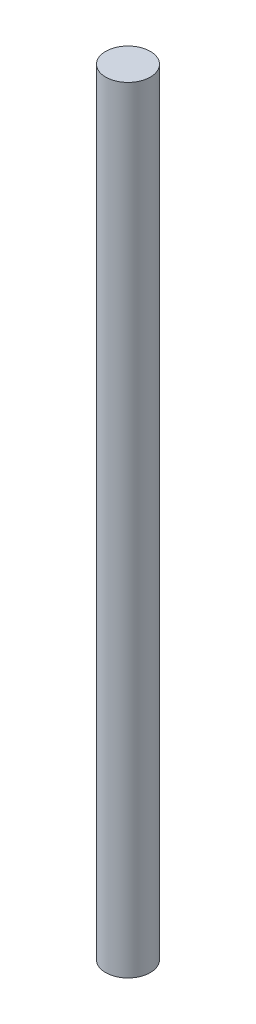
SolidWorks part; units mm, degrees
material "ALUMINUM 6061-T6"
ref_plane "Front Plane" through (0, 0, 0) normal (0, 0, 1) x (1, 0, 0)
ref_plane "Top Plane" through (0, 0, 0) normal (0, 1, 0) x (1, 0, 0)
ref_plane "Right Plane" through (0, 0, 0) normal (1, 0, 0) x (0, 0, -1)
sketch "Sketch1" plane through (0, 0, 0) normal (0, 1, 0) x (1, 0, 0)
  circle A0 centre (0, 0) radius 9.4996
extrude "Boss-Extrude1" add sketch "Sketch1" along normal mid plane 330.2
